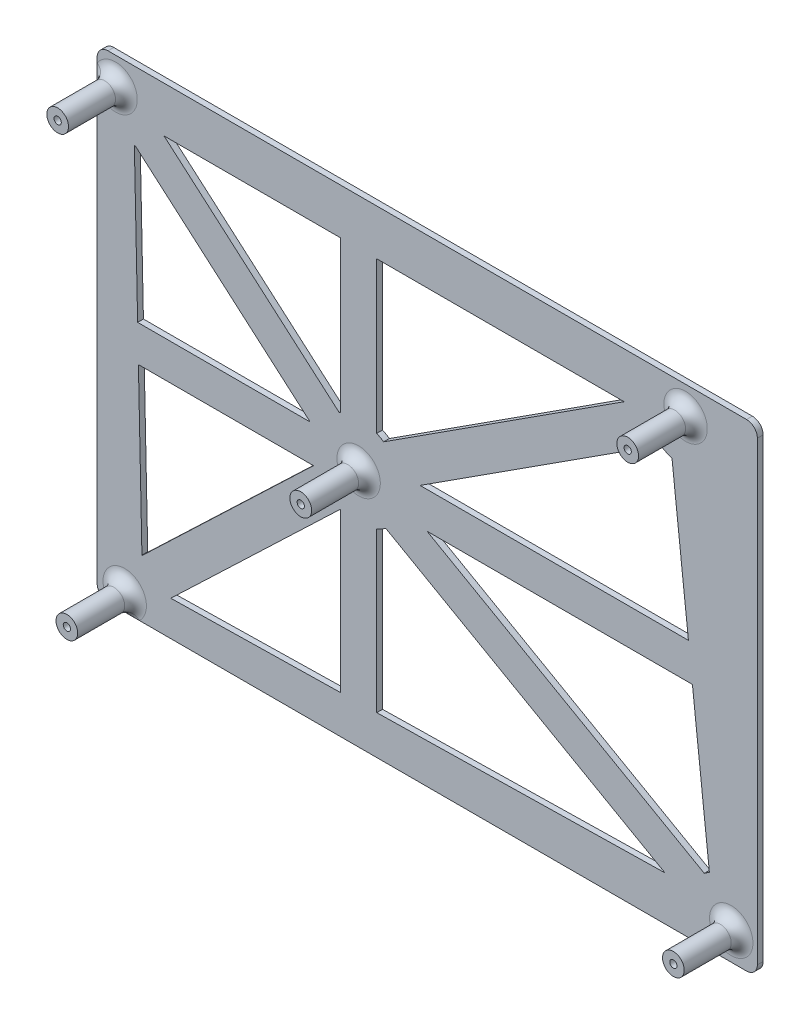
SolidWorks part; units mm, degrees
ref_plane "Front Plane" through (0, 0, 0) normal (0, 0, 1) x (1, 0, 0)
ref_plane "Top Plane" through (0, 0, 0) normal (0, 1, 0) x (1, 0, 0)
ref_plane "Right Plane" through (0, 0, 0) normal (1, 0, 0) x (0, 0, -1)
sketch "Model" plane through (0, 0, 0) normal (0, 0, 1) x (1, 0, 0)
  line L0 (-2.54, -132.08) -> (180, -132.08)
  line L1 (180, -132.08) -> (180, 0)
  line L2 (-2.54, 0) -> (180, 0)
  line L3 (-2.54, -132.08) -> (-2.54, 0)
  circle A2 centre (5.08, -127.635) radius 1
  circle A5 centre (2.54, -7.62) radius 1
  circle A6 centre (160.1498, -7.6751) radius 1
  circle A7 centre (172.7746, -124.4999) radius 1
  circle A8 centre (69.7499, -65.9249) radius 1
  dimension "D1" = 2
extrude "Boss-Extrude1" add sketch "Model" along normal blind 1.6
sketch "Sketch2" plane through (0, 0, 1.6) normal (0, 0, 1) x (1, 0, 0)
  circle A0 centre (2.54, -7.62) radius 3
  circle A2 centre (69.7499, -65.9249) radius 3
  circle A4 centre (160.1498, -7.6751) radius 3
  circle A6 centre (5.08, -127.635) radius 3
  circle A7 centre (172.7746, -124.4999) radius 3
  circle A8 centre (2.54, -7.62) radius 1 construction
  circle A10 centre (160.1498, -7.6751) radius 1 construction
  circle A12 centre (69.7499, -65.9249) radius 1 construction
  circle A14 centre (5.08, -127.635) radius 1 construction
  circle A15 centre (172.7746, -124.4999) radius 1 construction
  circle A16 centre (2.54, -7.62) radius 1
  circle A18 centre (160.1498, -7.6751) radius 1
  circle A20 centre (69.7499, -65.9249) radius 1
  circle A22 centre (5.08, -127.635) radius 1
  circle A23 centre (172.7746, -124.4999) radius 1
  dimension "D1" = 6
extrude "Boss-Extrude2" add sketch "Sketch2" along normal blind 16
fillet "Fillet2" radius 3 9 edges at (-2.54, 0, 0.8) (180, 0, 0.8) (180, -132.08, 0.8) (-2.54, -132.08, 0.8) (169.7746, -124.4999, 1.6) (157.1498, -7.6751, 1.6) (2.08, -127.635, 1.6) (-0.46, -7.62, 1.6) (66.7499, -65.9249, 1.6)
sketch "Sketch3" plane through (0, 0, 1.6) normal (0, 0, 1) x (1, 0, 0)
  line L1 (8.6478, -60.9249) -> (7.7436, -18.9854)
  line L2 (162.0408, -70.9249) -> (166.7372, -113.6091)
  line L3 (9.8369, -116.0755) -> (8.8634, -70.9249)
  line L4 (153.2277, -18.0835) -> (86.7407, -60.9249)
  line L5 (64.7499, -121.5186) -> (64.7499, -77.6072)
  line L6 (15.9392, -12.6247) -> (64.7499, -12.6418)
  line L7 (15.9392, -12.6247) -> (64.3725, -54.6407)
  line L10 (74.7499, -121.3316) -> (74.7499, -77.3814)
  line L11 (160.9406, -60.9249) -> (86.7407, -60.9249)
  line L12 (88.6605, -70.9249) -> (165.3318, -114.5166)
  line L13 (143.1683, -12.6692) -> (76.672, -55.5165)
  line L15 (7.9175, -18.9042) -> (56.3561, -60.9249)
  line L17 (162.0408, -70.9249) -> (88.6605, -70.9249)
  line L18 (156.3935, -19.5974) -> (160.9406, -60.9249)
  line L19 (154.4646, -119.8413) -> (74.7499, -121.3316)
  line L22 (64.7499, -121.5186) -> (17.8128, -122.3961)
  line L25 (74.7499, -12.6453) -> (143.1683, -12.6692)
  line L26 (64.7499, -54.4685) -> (64.7499, -12.6418)
  line L30 (56.3561, -60.9249) -> (8.6478, -60.9249)
  line L36 (57.2675, -70.9249) -> (9.9166, -116.1086)
  line L38 (57.2675, -70.9249) -> (8.8634, -70.9249)
  line L43 (64.7499, -77.6072) -> (17.8128, -122.3961)
  line L48 (77.2379, -75.9339) -> (154.4646, -119.8413)
  line L61 (74.7499, -54.4685) -> (74.7499, -12.6453)
  arc A0 (7.7436, -18.9854) -> (7.9175, -18.9042) centre (2.54, -7.62) ccw
  arc A2 (153.2277, -18.0835) -> (156.3935, -19.5974) centre (160.1498, -7.6751) ccw
  arc A3 (166.7372, -113.6091) -> (165.3318, -114.5166) centre (172.7746, -124.4999) ccw
  arc A4 (9.9166, -116.1086) -> (9.8369, -116.0755) centre (5.08, -127.635) ccw
  arc A6 (64.7499, -54.4685) -> (64.3725, -54.6407) centre (69.7499, -65.9249) ccw
  arc A7 (76.672, -55.5165) -> (74.7499, -54.4685) centre (69.7499, -65.9249) ccw
  arc A10 (74.7499, -77.3814) -> (77.2379, -75.9339) centre (69.7499, -65.9249) ccw
  dimension "D1" = 25
extrude "Cut-Extrude1" cut sketch "Sketch3" against normal blind 16
